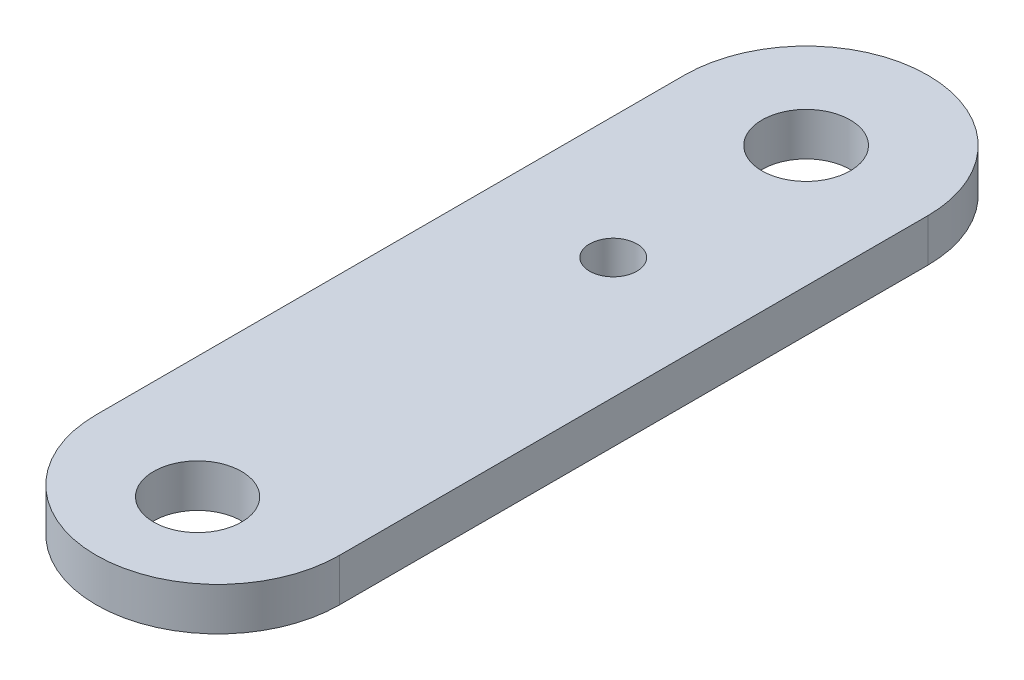
SolidWorks part; units mm, degrees
material "Copper"
ref_plane "Front Plane" through (0, 0, 0) normal (0, 0, 1) x (1, 0, 0)
ref_plane "Top Plane" through (0, 0, 0) normal (0, 1, 0) x (1, 0, 0)
ref_plane "Right Plane" through (0, 0, 0) normal (1, 0, 0) x (0, 0, -1)
sketch "Sketch1" plane through (0, 0, 0) normal (0, 1, 0) x (1, 0, 0)
  line L1 (9, 1.5) -> (9, 45)
  line L4 (-9, 1.5) -> (-9, 45)
  line L5 (0, 0) -> (0, 1.5) construction
  circle A0 centre (0, 0) radius 3.25
  arc A1 (-9, 1.5) -> (9, 1.5) centre (0, 1.5) ccw
  arc A3 (-9, 45) -> (9, 45) centre (0, 45) cw
  circle A4 centre (0, 45) radius 3.2639
  point P7 (0, 4.4928)
  dimension "D1" = 6.5
  dimension "D2" = 18
  dimension "D4" = 45
  dimension "D5" = 1.5
  dimension "D3" = 6.5278
base flange "Base-Flange1" sketch "Sketch1" thickness 3.175 reverse thickness direction no parameters "D1"=0.7366
sketch "Sketch2" plane through (0, -3.175, 0) normal (0, -1, 0) x (1, 0, 0)
  circle A0 centre (0.05, -30.6875) radius 1.75
extrude "Cut-Extrude1" cut sketch "Sketch2" against normal up to next
sketch "Bend-Lines1" [suppressed] plane through (0, 0, 0) normal (0, 1, 0) x (1, 0, 0)
sketch "Bounding-Box1" [suppressed] plane through (0, 0, 0) normal (0, 1, 0) x (1, 0, 0)
sheet metal parameters "Sheet-Metal1" thickness 3.175 parameters "D1"=0.7366
flat pattern "Flat-Pattern1" [suppressed]
sketch "Bend-Lines2" plane through (0, 0, 0) normal (0, 1, 0) x (1, 0, 0)
sketch3d "Bounding-Box2" [suppressed]
  line L0 (-9, 52.4999, 0) -> (-9, -8.9999, 0) construction
  line L1 (9, 52.4999, 0) -> (9, -8.9999, 0) construction
  line L2 (-9, 52.4999, 0) -> (9, 52.4999, 0) construction
  line L3 (-9, -8.9999, 0) -> (9, -8.9999, 0) construction
sheet metal parameters "Sheet-Metal7" thickness 3.175 parameters "D1"=0.7366
flat pattern "Flat-Pattern1" [suppressed]
sketch "Bend-Lines2" plane through (0, 0, 0) normal (0, 1, 0) x (1, 0, 0)
sketch3d "Bounding-Box2" [suppressed]
  line L0 (-9, 52.4999, 0) -> (-9, -8.9999, 0) construction
  line L1 (9, 52.4999, 0) -> (9, -8.9999, 0) construction
  line L2 (-9, 52.4999, 0) -> (9, 52.4999, 0) construction
  line L3 (-9, -8.9999, 0) -> (9, -8.9999, 0) construction
